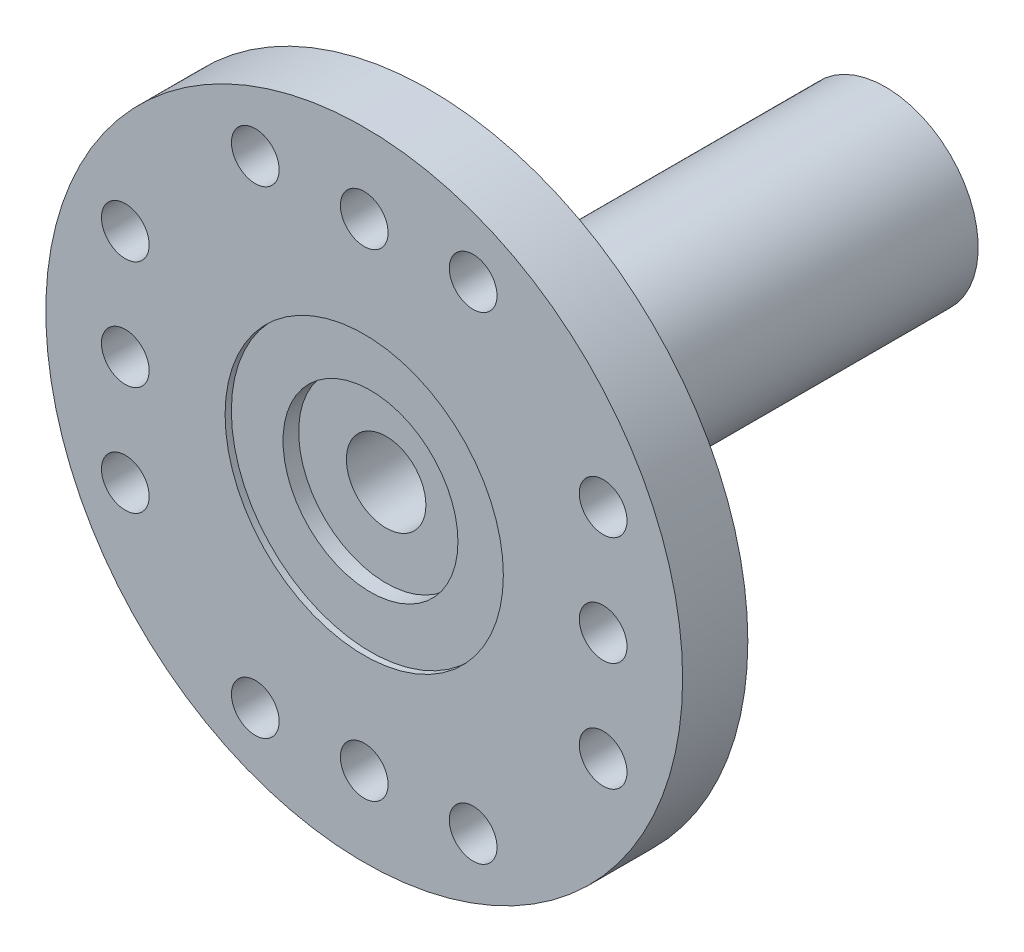
SolidWorks part; units mm, degrees
material "PS Medium/High Flow"
ref_plane "Front Plane" through (0, 0, 0) normal (0, 0, 1) x (1, 0, 0)
ref_plane "Top Plane" through (0, 0, 0) normal (0, 1, 0) x (1, 0, 0)
ref_plane "Right Plane" through (0, 0, 0) normal (1, 0, 0) x (0, 0, -1)
sketch "Sketch1" plane through (0, 0, 0) normal (0, 0, 1) x (1, 0, 0)
  circle A0 centre (0, 0) radius 10.1727
  dimension "D1" = 20.3454
extrude "Extrude1" add sketch "Sketch1" along normal blind 2.0828
sketch "Sketch2" plane through (0, 0, 0) normal (0, 0, -1) x (-1, 0, 0)
  circle A0 centre (0, 0) radius 4.699
  dimension "D1" = 9.398
extrude "Extrude2" add sketch "Sketch2" along normal blind 3.302
sketch "Sketch3" plane through (0, 0, -3.302) normal (0, 0, -1) x (-1, 0, 0)
  circle A0 centre (0, 0) radius 2.9591
  dimension "D1" = 5.9182
extrude "Extrude3" add sketch "Sketch3" along normal blind 11.27
sketch "Sketch4" plane through (0, 0, 2.0828) normal (0, 0, 1) x (1, 0, 0)
  circle A0 centre (0, 0) radius 4.445
  dimension "D1" = 8.89
extrude "Cut-Extrude1" cut sketch "Sketch4" against normal blind 0.2
sketch "Sketch6" plane through (0, 0, 1.8828) normal (0, 0, 1) x (1, 0, 0)
  circle A0 centre (0, 0) radius 2.794
  dimension "D1" = 5.588
extrude "Cut-Extrude2" cut sketch "Sketch6" against normal blind 0.5
sketch "Sketch7" plane through (0, 0, 1.3828) normal (0, 0, 1) x (1, 0, 0)
  circle A0 centre (0, 0) radius 1.27
  dimension "D1" = 2.54
extrude "Cut-Extrude3" cut sketch "Sketch7" against normal through all
sketch "Sketch8" plane through (0, 0, 2.0828) normal (0, 0, 1) x (1, 0, 0)
  line L0 (0, 0) -> (10.1727, 0) construction
  line L1 (7.6327, 0) -> (7.6327, -6.725) construction
  circle A0 centre (0, 0) radius 10.1727 construction
  circle A1 centre (7.6327, 0) radius 0.762
  circle A2 centre (7.6327, -3.4798) radius 0.762
  circle A3 centre (7.6327, 3.4798) radius 0.762
  dimension "D1" = 1.524
  dimension "D3" = 3.4798
  dimension "D4" = 4.3082
  dimension "D2" = 2.54
ref_axis "Axis1" through (0, 0, 9.495) along (0, 0, -1)
extrude "Cut-Extrude4" cut sketch "Sketch8" against normal up to next
pattern_circular "CirPattern1" count 4 over 360 about axis through (0, 0, 9.495) along (0, 0, -1) of "Cut-Extrude4"
